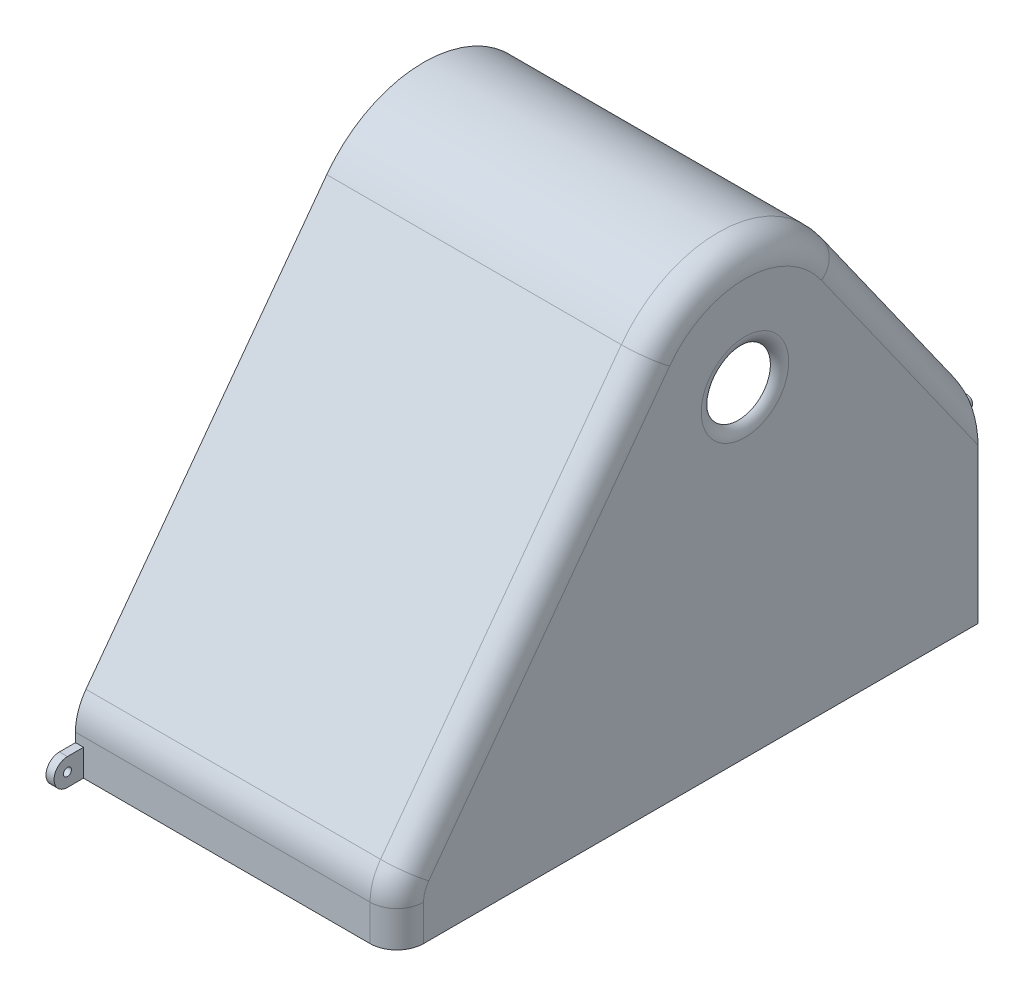
SolidWorks part; units mm, degrees
ref_plane "Alzado" through (0, 0, 0) normal (0, 0, 1) x (1, 0, 0)
ref_plane "Planta" through (0, 0, 0) normal (0, 1, 0) x (1, 0, 0)
ref_plane "Vista lateral" through (0, 0, 0) normal (1, 0, 0) x (0, 0, -1)
sketch "Croquis1" plane through (0, 0, 0) normal (1, 0, 0) x (0, 0, -1)
  line L0 (-200, 0) -> (200, 0)
  line L2 (17.0234, 70) -> (175, 70)
  line L3 (-200, 0) -> (-200, 20)
  line L4 (-200, 20) -> (-106.1703, 146.7714)
  line L5 (200, 0) -> (200, 45)
  line L6 (200, 45) -> (175, 70)
  line L7 (17.0234, 70) -> (17.0234, 75)
  line L8 (17.0234, 75) -> (-33.2796, 146.0118)
  arc A0 (-33.2796, 146.0118) -> (-106.1703, 146.7714) centre (-70, 120) ccw
  circle A1 centre (-70, 120) radius 12
  arc A3 (-106.1703, 146.7714) -> (-33.2796, 146.0118) centre (-70, 120) ccw construction
  point P3 (0, 0)
  dimension "D4" = 90
  dimension "D5" = 24
  dimension "D1" = 400
  dimension "D2" = 120
  dimension "D3" = 70
  dimension "D6" = 20
  dimension "D7" = 70
  dimension "D8" = 45
  dimension "D9" = 50.3031
  dimension "D10" = 45
  dimension "D11" = 5
extrude "Saliente-Extruir1" add sketch "Croquis1" against normal blind 120
sketch "Croquis2" plane through (-120, 0, 0) normal (-1, 0, 0) x (0, 0, 1)
  line L10 (102.9552, 144.3917) -> (196, 18.6807)
  line L11 (-196, 0) -> (-196, 43.3431)
  line L12 (200, 0) -> (-200, 0) construction
  line L13 (-196, 43.3431) -> (-173.3431, 66)
  line L14 (-173.3431, 66) -> (-33.0234, 66)
  line L15 (-33.0234, 66) -> (-33.0234, 60)
  line L16 (-33.0234, 60) -> (-13.0234, 60)
  line L17 (-13.0234, 60) -> (-13.0234, 73.7268)
  line L18 (-13.0234, 73.7268) -> (36.5437, 143.6997)
  line L19 (-17.0234, 75) -> (33.2796, 146.0118) construction
  line L20 (-175, 70) -> (-17.0234, 70) construction
  line L21 (-200, 45) -> (-175, 70) construction
  line L22 (-200, 0) -> (-200, 45) construction
  line L23 (-17.0234, 70) -> (-17.0234, 75) construction
  line L24 (196, 18.6807) -> (196, 0)
  line L25 (196, 0) -> (-196, 0)
  line L26 (106.1703, 146.7714) -> (200, 20) construction
  line L27 (200, 20) -> (200, 0) construction
  arc A3 (102.9552, 144.3917) -> (36.5437, 143.6997) centre (70, 120) ccw
  arc A4 (102.9552, 144.3917) -> (36.5437, 143.6997) centre (70, 120) ccw
  dimension "D1" = 10
  dimension "D3" = 4
  dimension "D4" = 4
  dimension "D5" = 4
  dimension "D6" = 20
  dimension "D7" = 4
  dimension "D8" = 4
  dimension "D2" = 4
extrude "Cortar-Extruir1" cut sketch "Croquis2" against normal offset from surface (117.5 mm away) 2.5 up to face at (0, 120, 58)
fillet "Redondeo1" radius 20 6 edges at (-60, 45, -200) (-60, 70, -175) (-60, 20, 200) (-61.25, 18.6807, 196) (-61.25, 66, -173.3431) (-61.25, 43.3431, -196)
sketch "Croquis3" plane through (0, 0, -17.0234) normal (0, 0, -1) x (-1, 0, 0)
  line L0 (185, 195) -> (-65, 195)
  line L1 (185, 195) -> (185, -55)
  line L2 (185, -55) -> (-65, -55)
  line L3 (-65, 195) -> (-65, -55)
  line L4 (185, 195) -> (-65, -55) construction
  line L5 (185, -55) -> (-65, 195) construction
  line L6 (120, 70) -> (0, 70) construction
  point P0 (60, 70)
  dimension "D1" = 250
  dimension "D2" = 250
extrude "Cortar-Extruir2" cut sketch "Croquis3" along normal through all
sketch "Croquis4" plane through (0, 0, -17.0234) normal (0, 0, -1) x (-1, 0, 0)
  line L0 (120, 60) -> (2.5, 60) construction
  line L1 (0, 0) -> (0, 75) construction
  circle A0 centre (40, 64) radius 2
  circle A1 centre (100, 64) radius 2
  dimension "D1" = 4
  dimension "D2" = 4
  dimension "D3" = 60
  dimension "D4" = 4
  dimension "D5" = 40
extrude "Cortar-Extruir3" cut sketch "Croquis4" against normal blind 20
sketch "Croquis5" plane through (0, 0, -17.0234) normal (0, 0, -1) x (-1, 0, 0)
  line L5 (120, 60) -> (2.5, 60) construction
  circle A0 centre (10, 64) radius 2
  circle A1 centre (70, 64) radius 2
  circle A2 centre (40, 64) radius 2 construction
  circle A3 centre (100, 64) radius 2 construction
  dimension "D1" = 4
  dimension "D2" = 4
  dimension "D8" = 30
  dimension "D7" = 30
  dimension "D9" = 4
extrude "Saliente-Extruir2" add sketch "Croquis5" along normal blind 6
fillet "Redondeo2" radius 10 10 edges at (0, 110.5059, 8.1281) (0, 6.7018, 200) (0, 19.6681, 198.9936) (0, 86.0367, 151.123) (0, 164.9976, 69.5311) (-2.5, 6.0422, 196) (-2.5, 18.3488, 194.9936) (-2.5, 108.7132, 11.7601) (-2.5, 160.9978, 69.5728) (-2.5, 84.1873, 147.5154)
fillet "Redondeo4" radius 20 2 edges at (-65, 75, -17.0234) (-66.25, 73.7268, -13.0234)
sketch "Croquis6" plane through (-120, 0, 0) normal (-1, 0, 0) x (0, 0, 1)
  line L20 (34.5037, 145.1448) -> (-12.1196, 79.3277)
  line L21 (-15.5234, 68.6339) -> (-15.5234, 61.5)
  line L22 (-15.5234, 61.5) -> (-14.5234, 61.5)
  line L23 (-14.5234, 61.5) -> (-14.5234, 67.3607)
  line L24 (-10.5676, 79.7886) -> (35.3197, 144.5667)
  line L25 (104.1609, 145.2841) -> (193.2814, 24.8752)
  line L26 (197.5, 12.0844) -> (197.5, 1.5)
  line L27 (197.5, 1.5) -> (198.5, 1.5)
  line L28 (198.5, 1.5) -> (198.5, 13.4036)
  line L29 (194.87, 24.4097) -> (104.9646, 145.879)
  line L30 (34.5037, 145.1448) -> (-12.1196, 79.3277)
  line L31 (-15.5234, 68.6339) -> (-15.5234, 61.5)
  line L32 (-15.5234, 61.5) -> (-14.5234, 61.5)
  line L33 (-14.5234, 61.5) -> (-14.5234, 67.3607)
  line L34 (-10.5676, 79.7886) -> (35.3197, 144.5667)
  line L35 (104.1609, 145.2841) -> (193.2814, 24.8752)
  line L36 (197.5, 12.0844) -> (197.5, 1.5)
  line L37 (197.5, 1.5) -> (198.5, 1.5)
  line L38 (198.5, 1.5) -> (198.5, 13.4036)
  line L39 (194.87, 24.4097) -> (104.9646, 145.879)
  arc A6 (-10.5676, 79.7886) -> (-14.5234, 67.3607) centre (6.9766, 67.3607) ccw
  arc A7 (-10.5676, 79.7886) -> (-14.5234, 67.3607) centre (6.9766, 67.3607) ccw
  arc A10 (-12.1196, 79.3277) -> (-15.5234, 68.6339) centre (2.9766, 68.6339) ccw
  arc A11 (104.1609, 145.2841) -> (35.3197, 144.5667) centre (70, 120) ccw
  arc A12 (197.5, 12.0844) -> (193.2814, 24.8752) centre (176, 12.0844) ccw
  arc A13 (198.5, 13.4036) -> (194.87, 24.4097) centre (180, 13.4036) ccw
  arc A14 (104.9646, 145.879) -> (34.5037, 145.1448) centre (70, 120) ccw
  arc A15 (-12.1196, 79.3277) -> (-15.5234, 68.6339) centre (2.9766, 68.6339) ccw
  arc A16 (104.1609, 145.2841) -> (35.3197, 144.5667) centre (70, 120) ccw
  arc A17 (197.5, 12.0844) -> (193.2814, 24.8752) centre (176, 12.0844) ccw
  arc A18 (198.5, 13.4036) -> (194.87, 24.4097) centre (180, 13.4036) ccw
  arc A19 (104.9646, 145.879) -> (34.5037, 145.1448) centre (70, 120) ccw
  dimension "D1" = 1.5
extrude "Cortar-Extruir4" cut sketch "Croquis6" against normal blind 4
sketch "Croquis7" plane through (0, 0, 0) normal (0, -1, 0) x (1, 0, 0)
  line L0 (-2.5, 75) -> (-5, 75)
  line L1 (-2.5, 111) -> (-2.5, 29) construction
  line L2 (-5, 65) -> (-2.5, 65)
  line L3 (-2.5, 65) -> (-2.5, 75)
  line L4 (0, 190) -> (0, -17.0234) construction
  circle A0 centre (-5, 70) radius 2.25
  arc A2 (-5, 65) -> (-5, 75) centre (-5, 70) cw
  point P3 (-15.1715, 60.2586)
  point P9 (-15.7927, 64.6988)
  point P12 (0, 0)
  dimension "D2" = 4.5
  dimension "D1" = 10
  dimension "D3" = 5
  dimension "D4" = 70
extrude "Saliente-Extruir3" add sketch "Croquis7" against normal blind 6
sketch "Croquis8" plane through (-120, 0, 0) normal (-1, 0, 0) x (0, 0, 1)
  line L0 (200, 0) -> (206, 0)
  line L1 (206, 10) -> (200, 10)
  line L2 (200, 13.4036) -> (200, 0) construction
  line L3 (200, 10) -> (200, 0)
  line L4 (196, 0) -> (196, 12.0844) construction
  arc A0 (206, 0) -> (206, 10) centre (206, 5) ccw
  circle A1 centre (206, 5) radius 1.5
  dimension "D1" = 3
  dimension "D2" = 10
  dimension "D3" = 10
extrude "Saliente-Extruir4" add sketch "Croquis8" against normal blind 3
sketch "Croquis9" plane through (0, 0, -17.0234) normal (0, 0, -1) x (-1, 0, 0)
  line L0 (2.5, 25) -> (7, 25)
  line L1 (2.5, 50.7802) -> (2.5, 0) construction
  line L2 (7, 15) -> (2.5, 15)
  line L3 (2.5, -7.9156) -> (2.5, 32.0844) construction
  line L4 (2.5, 15) -> (2.5, 25)
  line L5 (0, 0) -> (0, 57.7002) construction
  arc A0 (7, 25) -> (7, 15) centre (7, 20) cw
  circle A1 centre (7, 20) radius 2
  point P10 (0, 0)
  dimension "D1" = 4
  dimension "D2" = 10
  dimension "D3" = 7
  dimension "D4" = 20
extrude "Saliente-Extruir5" add sketch "Croquis9" against normal blind 3
fillet "Redondeo5" radius 5 1 edges at (0, 120, 58)
